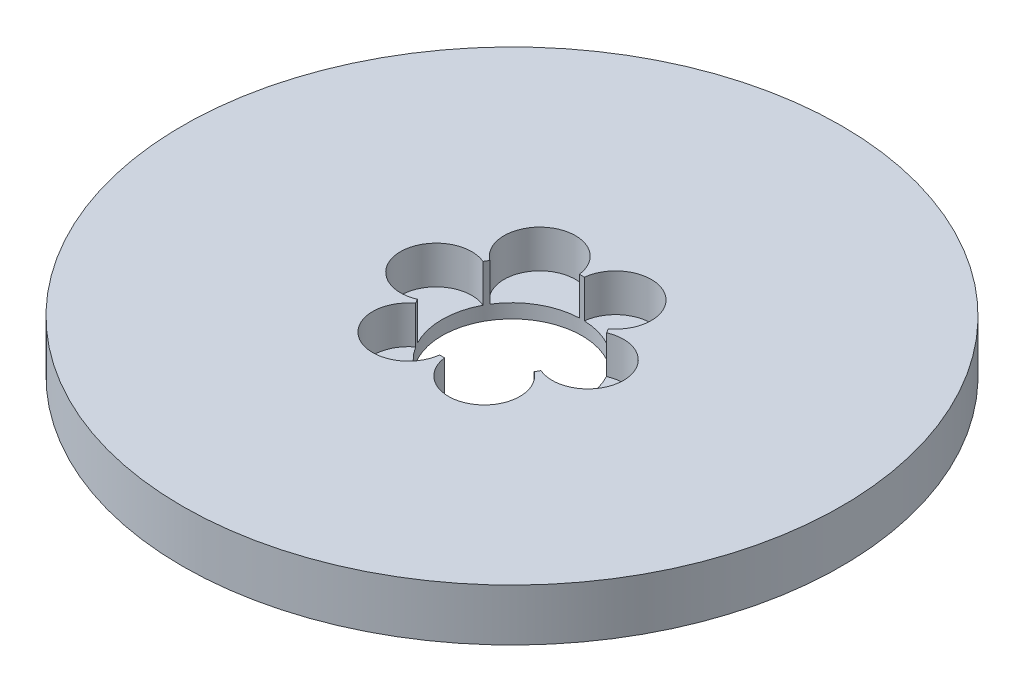
SolidWorks part; units mm, degrees
ref_plane "Front Plane" through (0, 0, 0) normal (0, 0, 1) x (1, 0, 0)
ref_plane "Top Plane" through (0, 0, 0) normal (0, 1, 0) x (1, 0, 0)
ref_plane "Right Plane" through (0, 0, 0) normal (1, 0, 0) x (0, 0, -1)
sketch "Sketch1" plane through (0, 0, 0) normal (0, 1, 0) x (1, 0, 0)
  circle A0 centre (0, 0) radius 82.5
  dimension "FLANGE_OD" = 165
extrude "Boss-Extrude1" add sketch "Sketch1" along normal blind 13
sketch "Sketch2" plane through (0, 0, 0) normal (0, 1, 0) x (1, 0, 0)
  circle A0 centre (0, 0) radius 17.5
  dimension "BORE_D" = 35
extrude "Cut-Extrude1" cut sketch "Sketch2" along normal through all
sketch "Sketch3" plane through (0, 13, 0) normal (0, 1, 0) x (1, 0, 0)
  circle A0 centre (0, 0) radius 18.9892 construction
  circle A1 centre (-18.9892, 0) radius 8.9317
  dimension "BOLT_D" = 17.8633
  dimension "BOLT_PCD" = 37.9783
extrude "Cut-Extrude2" cut sketch "Sketch3" against normal blind 9.4871
pattern_circular "CirPattern1" count 6 over 360 about axis through (0, 0, 0) along (0, 1, 0) of "Cut-Extrude2"
